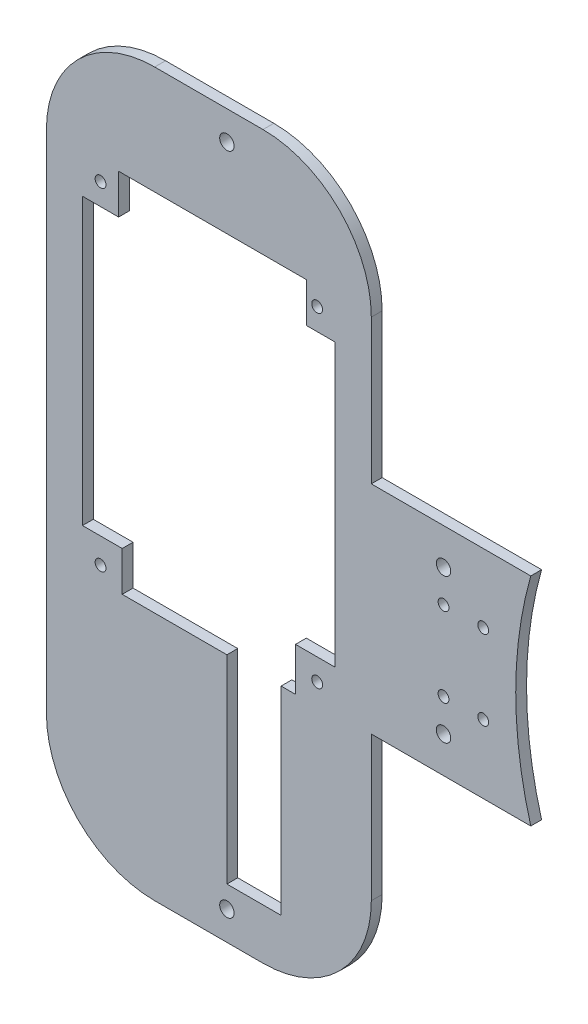
SolidWorks part; units mm, degrees
material "Caoba"
ref_plane "Alzado" through (0, 0, 0) normal (0, 0, 1) x (1, 0, 0)
ref_plane "Planta" through (0, 0, 0) normal (0, 1, 0) x (1, 0, 0)
ref_plane "Vista lateral" through (0, 0, 0) normal (1, 0, 0) x (0, 0, -1)
sketch "Croquis1" plane through (0, 0, 0) normal (0, 0, 1) x (1, 0, 0)
  circle A0 centre (0, 0) radius 100
  dimension "D1" = 200
extrude "Saliente-Extruir1" add sketch "Croquis1" along normal blind 3
sketch "Croquis3" plane through (0, 0, 3) normal (0, 0, 1) x (1, 0, 0)
  line L0 (0, 0) -> (190, 0) construction
  circle A0 centre (190, 0) radius 110
  dimension "D1" = 220
  dimension "D2" = 190
extrude "Cortar-Extruir1" cut sketch "Croquis3" against normal blind 3
fillet "Redondeo1" radius 10 2 edges at (89.4737, -44.6594, 1.5) (89.4737, 44.6594, 1.5)
sketch "Croquis12" plane through (0, 0, 0) normal (0, 0, -1) x (-1, 0, 0)
  line L0 (-80, 0) -> (100, 0) construction
  line L1 (-71, 0) -> (-71, -11) construction
  line L2 (-71, 0) -> (-71, 11) construction
  line L3 (0, 100) -> (0, -100) construction
  line L5 (-60, 11) -> (-60, -11) construction
  circle A4 centre (-71, 11) radius 1.5
  arc A5 (-87.1345, -49.0671) -> (-87.1345, 49.0671) centre (0, 0) ccw construction
  circle A6 centre (-71, -11) radius 1.5
  circle A7 centre (-60, 11) radius 1.5
  circle A8 centre (-60, -11) radius 1.5
  arc A11 (-87.7193, -40.4803) -> (-87.7193, 40.4803) centre (-190, 0) ccw construction
  arc A12 (-87.1345, -49.0671) -> (-87.1345, 49.0671) centre (0, 0) ccw construction
  dimension "D4" = 11
  dimension "D5" = 3
  dimension "D6" = 3
  dimension "D7" = 11
  dimension "D1" = 3
  dimension "D2" = 3
  dimension "D3" = 60
  dimension "D8" = 11
  dimension "D9" = 22
  dimension "D10" = 11
extrude "Cortar-Extruir6" cut sketch "Croquis12" against normal through all
sketch "Croquis13" plane through (0, 0, 0) normal (0, 0, -1) x (-1, 0, 0)
  line L0 (0, 100) -> (0, -100) construction
  line L1 (100, 0) -> (-100, 0) construction
  line L2 (-70.7107, -70.7107) -> (70.7107, 70.7107) construction
  line L3 (-70.7093, 70.7093) -> (70.712, -70.712) construction
  line L4 (-70.7093, 70.7093) -> (-70.7107, -70.7107) construction
  line L5 (-70.7107, -70.7107) -> (70.712, -70.712) construction
  line L6 (70.712, -70.712) -> (70.7107, 70.7107) construction
  line L7 (70.7107, 70.7107) -> (-70.7093, 70.7093) construction
  arc A2 (-87.1345, -49.0671) -> (-87.1345, 49.0671) centre (0, 0) ccw construction
  circle A3 centre (0, 92) radius 2
  circle A4 centre (0, -92) radius 2
  circle A7 centre (70.7111, 30) radius 2
  circle A8 centre (70.7116, -30) radius 2
  circle A11 centre (-60, 20) radius 2
  circle A12 centre (-60, -20) radius 2
  arc A13 (-87.1345, -49.0671) -> (-87.1345, 49.0671) centre (0, 0) ccw construction
  dimension "D10" = 4
  dimension "D11" = 92
  dimension "D12" = 4
  dimension "D13" = 92
  dimension "D14" = 4
  dimension "D15" = 4
  dimension "D16" = 30
  dimension "D17" = 30
  dimension "D18" = 4
  dimension "D19" = 4
  dimension "D20" = 20
  dimension "D21" = 20
  dimension "D22" = 60
  dimension "D23" = 40
  dimension "D24" = 21.2886
  dimension "D25" = 21.29
  dimension "D1" = 200
  dimension "D2" = 0
  dimension "D3" = 0
  dimension "D4" = 200
  dimension "D5" = 200
  dimension "D6" = 45
  dimension "D7" = 45
  dimension "D8" = 141.42
  dimension "D9" = 141.42
extrude "Cortar-Extruir7" cut sketch "Croquis13" against normal through all
sketch "Croquis19" plane through (0, 0, 0) normal (0, 0, -1) x (-1, 0, 0)
  line L1 (50, 95) -> (125, 95)
  line L2 (50, 95) -> (50, -95)
  line L3 (50, -95) -> (125, -95)
  line L4 (125, 95) -> (125, -95)
  line L6 (-95, -30) -> (-40, -30)
  line L7 (-95, -30) -> (-95, -102)
  line L8 (-95, -102) -> (-40, -102)
  line L9 (-40, -30) -> (-40, -102)
  line L10 (-95, 102) -> (-40, 102)
  line L11 (-95, 102) -> (-95, 30)
  line L12 (-95, 30) -> (-40, 30)
  line L13 (-40, 102) -> (-40, 30)
  dimension "D1" = 50
  dimension "D2" = 75
  dimension "D3" = 95
  dimension "D4" = 95
  dimension "D5" = 72
  dimension "D6" = 55
  dimension "D7" = 90
  dimension "D8" = 30
  dimension "D9" = 72
  dimension "D10" = 55
  dimension "D11" = 90
  dimension "D12" = 30
extrude "Cortar-Extruir11" cut sketch "Croquis19" against normal through all
sketch "Croquis20" plane through (0, 0, 0) normal (0, 0, -1) x (-1, 0, 0)
  line L0 (-80, 0) -> (50, 0) construction
  line L1 (50, 86.6025) -> (50, -86.6025) construction
  line L2 (0, 100) -> (0, -100) construction
  arc A0 (-84.1699, -30) -> (-84.1699, 30) centre (-190, 0) ccw construction
  arc A3 (50, 86.6025) -> (-40, 91.6515) centre (0, 0) ccw construction
  arc A4 (-40, -91.6515) -> (50, -86.6025) centre (0, 0) ccw construction
  circle A5 centre (-25, 65) radius 1.5
  circle A6 centre (35, -27) radius 1.5
  dimension "D1" = 3
  dimension "D2" = 3
  dimension "D3" = 65
  dimension "D4" = 27
  dimension "D5" = 35
  dimension "D6" = 25
extrude "Cortar-Extruir12" cut sketch "Croquis20" against normal through all
sketch "Croquis21" plane through (0, 0, 0) normal (0, 0, -1) x (-1, 0, 0)
  line L1 (-30, 70) -> (40, 70)
  line L2 (-30, 70) -> (-30, -31)
  line L3 (-30, -31) -> (40, -31)
  line L4 (40, 70) -> (40, -31)
  line L5 (-30, 70) -> (-22, 70)
  line L6 (-30, 70) -> (-30, 59)
  line L7 (-30, 59) -> (-22, 59)
  line L8 (-22, 70) -> (-22, 59)
  line L9 (40, -31) -> (29, -31)
  line L10 (40, -31) -> (40, -20)
  line L11 (40, -20) -> (29, -20)
  line L12 (29, -31) -> (29, -20)
  line L13 (40, 70) -> (30, 70)
  line L14 (40, 70) -> (40, 59)
  line L15 (40, 59) -> (30, 59)
  line L16 (30, 70) -> (30, 59)
  line L17 (-30, -31) -> (-19, -31)
  line L18 (-30, -31) -> (-30, -19)
  line L19 (-30, -19) -> (-19, -19)
  line L20 (-19, -31) -> (-19, -19)
  circle A0 centre (-25, 65) radius 1.5 construction
  circle A1 centre (35, -27) radius 1.5 construction
  circle A2 centre (35, 65) radius 1.5
  circle A3 centre (-25, -25) radius 1.5
  dimension "D2" = 5
  dimension "D7" = 11
  dimension "D9" = 3
  dimension "D10" = 5
  dimension "D11" = 5
  dimension "D12" = 5
  dimension "D14" = 3
  dimension "D15" = 6
  dimension "D16" = 5
  dimension "D17" = 6
  dimension "D5" = 11
  dimension "D1" = 5
  dimension "D3" = 101
  dimension "D4" = 70
  dimension "D6" = 3
  dimension "D8" = 11
  dimension "D13" = 11
  dimension "D18" = 19
extrude "Cortar-Extruir13" cut sketch "Croquis21" against normal blind 10 contours L3 L12 L11 L4 L1 L8 L7 L2 | A2 | A3 region at (-4.9626, 19.864, 0)
sketch "Croquis22" plane through (0, 0, 0) normal (0, 0, -1) x (-1, 0, 0)
  line L0 (50, 86.6025) -> (50, -86.6025) construction
  line L1 (-40, 100) -> (50, 100)
  line L2 (-40, 100) -> (-40, 80)
  line L3 (-40, 80) -> (50, 80)
  line L4 (50, 100) -> (50, 80)
  line L5 (-40, 30) -> (-40, 91.6515) construction
  line L6 (-80, 0) -> (50, 0) construction
  line L7 (50, -100) -> (50, -80)
  line L8 (-40, -100) -> (-40, -80)
  line L9 (-40, -100) -> (50, -100)
  line L10 (-40, -80) -> (50, -80)
  arc A0 (50, 86.6025) -> (-40, 91.6515) centre (0, 0) ccw construction
  arc A1 (-84.1699, -30) -> (-84.1699, 30) centre (-190, 0) ccw construction
  dimension "D1" = 0
  dimension "D2" = 20
  dimension "D3" = 100
extrude "Saliente-Extruir2" add sketch "Croquis22" against normal blind 3
sketch "Croquis23" plane through (0, 0, 0) normal (0, 0, -1) x (-1, 0, 0)
  line L1 (50, 100) -> (50, -100) construction
  line L3 (50, 100) -> (-40, 100) construction
  line L7 (-15, -31) -> (0, -31)
  line L8 (-15, -31) -> (-15, -86)
  line L9 (-15, -86) -> (0, -86)
  line L10 (0, -31) -> (0, -86)
  line L11 (-40, 30) -> (-40, 100) construction
  line L12 (50, 0) -> (-80, 0) construction
  line L13 (-19, -31) -> (29, -31) construction
  circle A0 centre (0, 92) radius 2
  arc A2 (-84.1699, -30) -> (-84.1699, 30) centre (-190, 0) ccw construction
  circle A3 centre (0, -92) radius 2
  point P23 (0, 0)
  line M2 (29, -31) -> (-19, -31)
  line M19 (-40, -100) -> (50, -100)
  dimension "D1" = 4
  dimension "D2" = 50
  dimension "D3" = 8
  dimension "D4" = 0
  dimension "D5" = 55
  dimension "D7" = 15
  dimension "D8" = 25
extrude "Cortar-Extruir14" cut sketch "Croquis23" against normal through all contours L10 A3 L8 M2 M19 | A3 | A0 region at (7.5, -58.5, 0) region at (0, 92, 0) region at (0, -92, 0)
fillet "Redondeo2" radius 30 4 edges at (-50, -100, 1.5) (40, -100, 1.5) (-50, 100, 1.5) (40, 100, 1.5)
